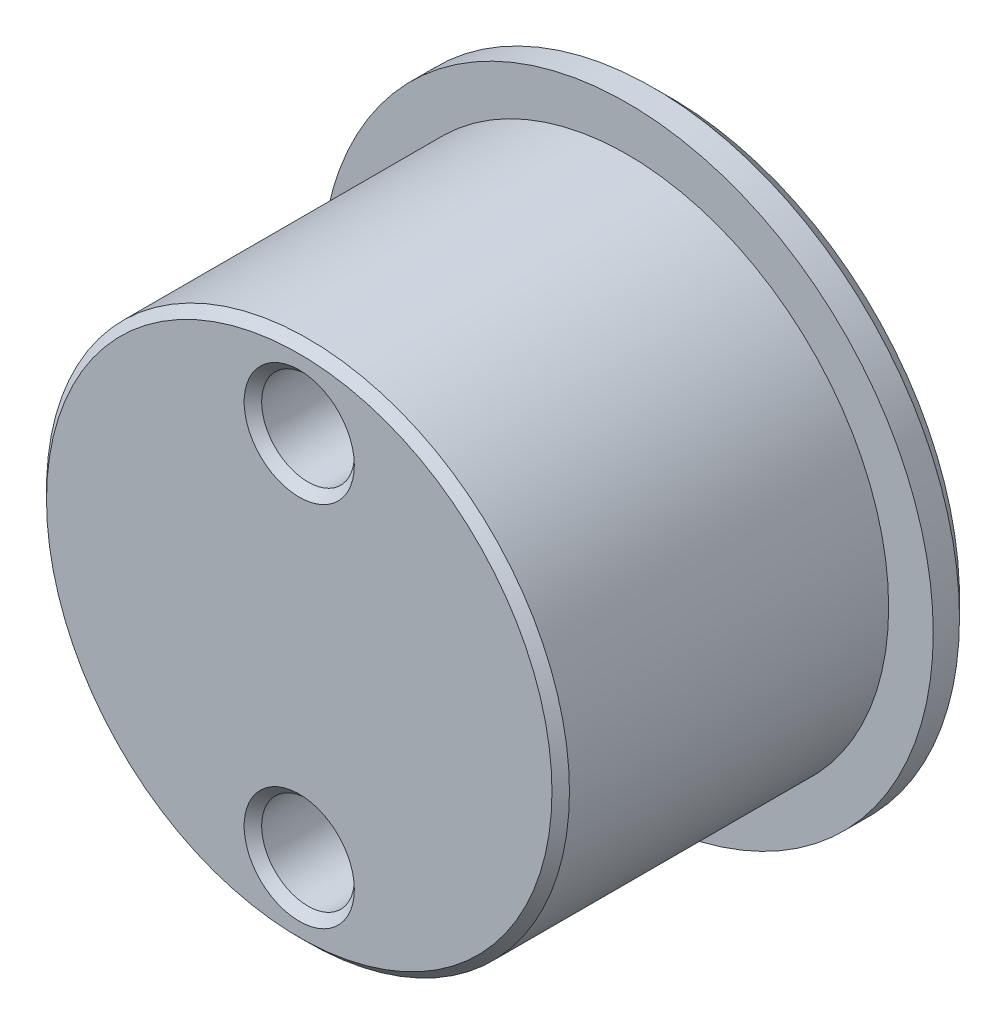
SolidWorks part; units mm, degrees
ref_plane "Front Plane" through (0, 0, 0) normal (0, 0, 1) x (1, 0, 0)
ref_plane "Top Plane" through (0, 0, 0) normal (0, 1, 0) x (1, 0, 0)
ref_plane "Right Plane" through (0, 0, 0) normal (1, 0, 0) x (0, 0, -1)
sketch "Sketch2" plane through (0, 0, 0) normal (0, 0, 1) x (1, 0, 0)
  line L0 (0, 20.6512) -> (0, 0) construction
  line L1 (0, 0) -> (19.945, 0) construction
  circle A0 centre (0, 0) radius 14.95
  circle A1 centre (0, 10.5) radius 2.65
  circle A2 centre (0, -10.5) radius 2.65
  dimension "D1" = 29.9
  dimension "D2" = 5.3
  dimension "D3" = 21
extrude "Boss-Extrude1" add sketch "Sketch2" along normal blind 18.75
sketch "Sketch3" plane through (0, 0, 0) normal (0, 0, -1) x (-1, 0, 0)
  circle A0 centre (0, 0) radius 17.5
  circle A1 centre (0, 10.5) radius 2.65
  circle A2 centre (0, -10.5) radius 2.65
  circle A3 centre (0, -10.5) radius 2.65 construction
  circle A4 centre (0, 10.5) radius 2.65 construction
  dimension "D1" = 35
  dimension "D2" = 0
extrude "Boss-Extrude2" add sketch "Sketch3" along normal blind 2.5
sketch "Sketch4" plane through (0, 0, -2.5) normal (0, 0, -1) x (-1, 0, 0)
  line L1 (4.7343, 10.5) -> (2.3671, 14.6)
  line L2 (2.3671, 14.6) -> (-2.3671, 14.6)
  line L3 (-2.3671, 14.6) -> (-4.7343, 10.5)
  line L4 (-4.7343, 10.5) -> (-2.3671, 6.4)
  line L5 (-2.3671, 6.4) -> (2.3671, 6.4)
  line L6 (2.3671, 6.4) -> (4.7343, 10.5)
  line L7 (4.7343, -10.5) -> (2.3671, -6.4)
  line L8 (2.3671, -6.4) -> (-2.3671, -6.4)
  line L9 (-2.3671, -6.4) -> (-4.7343, -10.5)
  line L10 (-4.7343, -10.5) -> (-2.3671, -14.6)
  line L11 (-2.3671, -14.6) -> (2.3671, -14.6)
  line L12 (2.3671, -14.6) -> (4.7343, -10.5)
  circle A0 centre (0, 10.5) radius 4.1 construction
  circle A1 centre (0, -10.5) radius 4.1 construction
  dimension "D1" = 8.2
extrude "Cut-Extrude1" cut sketch "Sketch4" against normal blind 6.4
chamfer "Chamfer1" distance 1 angle 45 1 edges at (-17.5, 0, -2.5)
sketch "Sketch5" plane through (0, 0, 3.9) normal (0, 0, -1) x (-1, 0, 0)
  circle A0 centre (0, 10.5) radius 2.65
  circle A1 centre (0, -10.5) radius 2.65
  circle A4 centre (0, -10.5) radius 2.65 construction
  circle A5 centre (0, 10.5) radius 2.65 construction
extrude "Boss-Extrude3" add sketch "Sketch5" against normal blind 0.2
chamfer "Chamfer2" distance 0.5 angle 45 15 edges at (-3.5507, -8.45, -2.5) (0, -6.4, -2.5) (3.5507, -8.45, -2.5) (3.5507, -12.55, -2.5) (0, -14.6, -2.5) (-3.5507, -12.55, -2.5) (-3.5507, 12.55, -2.5) (0, 14.6, -2.5) (3.5507, 12.55, -2.5) (3.5507, 8.45, -2.5) (0, 6.4, -2.5) (-3.5507, 8.45, -2.5) (14.95, 0, 18.75) (2.65, 10.5, 18.75) (-2.65, -10.5, 18.75)
